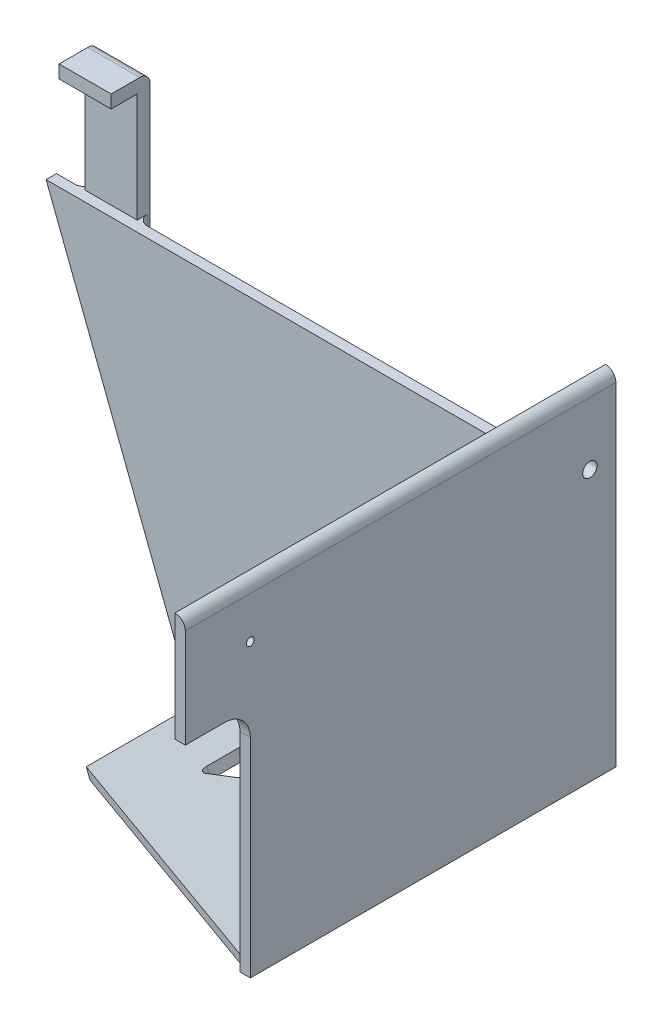
SolidWorks part; units mm, degrees
ref_plane "前视基准面" through (0, 0, 0) normal (0, 0, 1) x (1, 0, 0)
ref_plane "上视基准面" through (0, 0, 0) normal (0, 1, 0) x (1, 0, 0)
ref_plane "右视基准面" through (0, 0, 0) normal (1, 0, 0) x (0, 0, -1)
other "Configuration Table"
sketch "草图1" plane through (0, 0, 0) normal (1, 0, 0) x (0, 0, -1)
  line L1 (0, 0) -> (165.5, 0)
  line L2 (0, 0) -> (0, -132)
  line L3 (0, -132) -> (165.5, -132)
  line L4 (165.5, 0) -> (165.5, -132)
  dimension "D1" = 165.5
  dimension "D2" = 132
extrude "凸台-拉伸1" add sketch "草图1" along normal blind 4
sketch "草图3" plane through (0, 0, -165.5) normal (0, 0, -1) x (-1, 0, 0)
  line L0 (-4, -132) -> (211, -132)
  line L1 (211, -132) -> (211, -42)
  line L2 (211, -42) -> (-4, -42)
  line L3 (-4, -132) -> (-4, 0) construction
  line L4 (-4, -42) -> (-4, -132)
  line L5 (-4, 0) -> (0, 0) construction
  dimension "D1" = 42
  dimension "D3" = 215
extrude "凸台-拉伸2" add sketch "草图3" against normal blind 4
sketch "草图4" plane through (4, 0, 0) normal (1, 0, 0) x (0, 0, -1)
  line L0 (165.5, 0) -> (0, 0) construction
  line L1 (165.5, -132) -> (165.5, 0) construction
  circle A0 centre (155.5, -28) radius 2.75
  dimension "D1" = 28
  dimension "D3" = 5.5
  dimension "D2" = 10
extrude "切除-拉伸1" cut sketch "草图4" against normal blind 4
sketch "草图5" plane through (4, 0, 0) normal (1, 0, 0) x (0, 0, -1)
  line L0 (0, 0) -> (0, -132) construction
  line L1 (0, -42) -> (25, -42)
  line L2 (0, -42) -> (0, -132)
  line L3 (0, -132) -> (25, -132)
  line L4 (25, -42) -> (25, -132)
  line L5 (0, -132) -> (165.5, -132) construction
  line L6 (165.5, 0) -> (0, 0) construction
  dimension "D1" = 25
  dimension "D2" = 42
extrude "切除-拉伸2" cut sketch "草图5" against normal blind 10
fillet "圆角1" radius 10 1 edges at (2, -42, -25)
sketch "草图6" plane through (0, 0, -165.5) normal (0, 0, -1) x (-1, 0, 0)
  line L0 (211, -42) -> (176.3801, -132)
  line L1 (-4, -132) -> (211, -132) construction
  line L2 (176.3801, -132) -> (211, -132)
  line L3 (211, -132) -> (211, -42)
  dimension "D1" = 21.04
extrude "切除-拉伸3" cut sketch "草图6" against normal blind 10
sketch "草图7" plane through (0, 0, -165.5) normal (0, 0, -1) x (-1, 0, 0)
  line L0 (176.3801, -132) -> (153.13, -192.4425)
  line L1 (153.13, -192.4425) -> (-4, -132)
  line L3 (211, -42) -> (176.3801, -132) construction
  line L4 (-4, -132) -> (176.3801, -132)
extrude "凸台-拉伸3" add sketch "草图7" against normal blind 4
sketch "草图8" plane through (44.7466, -116.3262, 0) normal (0.359, -0.9333, 0) x (0.9333, 0.359, 0)
  line L0 (-43.6573, -165.5) -> (-43.6573, -25.5)
  line L1 (-43.6573, -25) -> (-43.6573, -161.5) construction
  line L2 (-43.6573, -25.5) -> (-212.0115, -120.5)
  line L3 (-212.0115, -120.5) -> (-212.0115, -165.5)
  line L4 (-212.0115, -165.5) -> (-43.6573, -165.5)
  dimension "D1" = 45
  dimension "D2" = 140
extrude "凸台-拉伸4" add sketch "草图8" against normal blind 4
sketch "草图9" plane through (4, 0, 0) normal (1, 0, 0) x (0, 0, -1)
  line L0 (165.5, 0) -> (0, 0) construction
  line L1 (0, 0) -> (0, -42) construction
  circle A0 centre (25, -20) radius 1.5
  dimension "D1" = 20
  dimension "D3" = 3
  dimension "D2" = 25
extrude "切除-拉伸4" cut sketch "草图9" against normal blind 4
fillet "圆角2" radius 4 1 edges at (4, 0, -82.75)
sketch "草图10" plane through (44.7466, -116.3262, 0) normal (0.359, -0.9333, 0) x (0.9333, 0.359, 0)
  line L1 (-172.0115, -125.5) -> (-152.0115, -125.5)
  line L2 (-172.0115, -125.5) -> (-172.0115, -145.5)
  line L3 (-172.0115, -145.5) -> (-152.0115, -145.5)
  line L4 (-152.0115, -125.5) -> (-152.0115, -145.5)
  dimension "D1" = 20
  dimension "D2" = 40
  dimension "D3" = 40
extrude "切除-拉伸5" cut sketch "草图10" against normal blind 4
fillet "圆角4" radius 4 4 edges at (-116.5149, -176.215, -145.5) (-116.5149, -176.215, -125.5) (-97.8483, -169.0346, -125.5) (-97.8483, -169.0346, -145.5)
sketch "草图11" plane through (0, 0, -165.5) normal (0, 0, -1) x (-1, 0, 0)
  line L1 (180, 5) -> (200, 5)
  line L2 (180, 5) -> (180, -55)
  line L3 (180, -55) -> (200, -55)
  line L4 (200, 5) -> (200, -55)
  dimension "D1" = 20
  dimension "D2" = 60
  dimension "D3" = 180
  dimension "D4" = 5
extrude "凸台-拉伸5" add sketch "草图11" along normal blind 5
fillet "圆角5" radius 4 3 edges at (-180, -48.5, -165.5) (-190, -55, -165.5) (-200, -48.5, -165.5)
fillet "圆角6" radius 4 1 edges at (-190, -55, -170.5)
sketch "草图12" plane through (0, 0, -165.5) normal (0, 0, 1) x (1, 0, 0)
  line L0 (-180, 5) -> (-180, -42) construction
  line L1 (-200, 5) -> (-180, 5)
  line L2 (-200, 5) -> (-200, 0)
  line L3 (-200, 0) -> (-180, 0)
  line L4 (-180, 5) -> (-180, 0)
  dimension "D1" = 5
extrude "凸台-拉伸6" add sketch "草图12" along normal blind 10
fillet "圆角7" radius 4 1 edges at (-190, 5, -170.5)
sketch "草图13" plane through (0, 0, -165.5) normal (0, 0, -1) x (-1, 0, 0)
  line L0 (48.4741, -124.6664) -> (77.1957, -50) construction
  line L1 (211, -42) -> (153.13, -192.4425) construction
  text T0 "Retail-Cart-3D-Model" font "微软雅黑" height 5
  dimension "D1" = 90
  dimension "D2" = 80
  dimension "D3" = 50
extrude "切除-拉伸6" cut sketch "草图13" against normal blind 0.5
